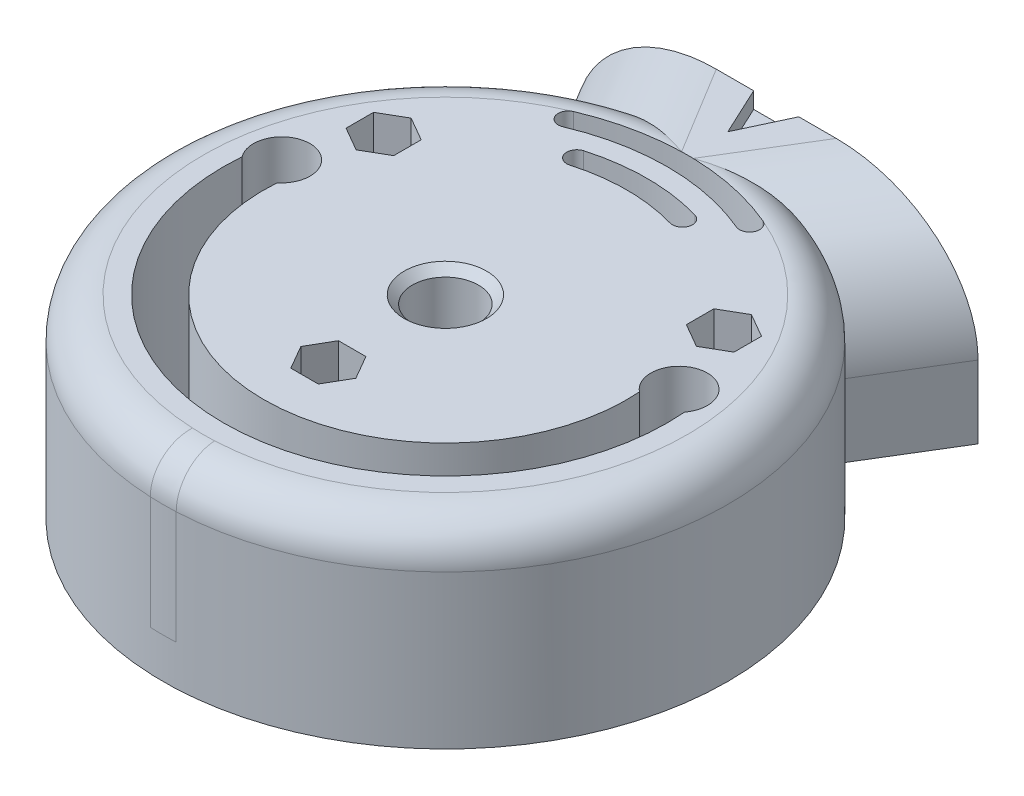
SolidWorks part; units mm, degrees
ref_plane "Alzado" through (0, 0, 0) normal (0, 0, 1) x (1, 0, 0)
ref_plane "Planta" through (0, 0, 0) normal (0, 1, 0) x (1, 0, 0)
ref_plane "Vista lateral" through (0, 0, 0) normal (1, 0, 0) x (0, 0, -1)
sketch "Croquis1" plane through (0, 0, 0) normal (0, 1, 0) x (1, 0, 0)
  line L0 (0, 35) -> (0, 41) construction
  line L1 (-35, 0) -> (-35, 35) construction
  line L2 (35, 0) -> (35, 35) construction
  line L3 (-35, 35) -> (35, 35) construction
  line L4 (0, 38) -> (-35, 38) construction
  line L5 (-35, 38) -> (35, 38) construction
  line L6 (35, 38) -> (35, 35) construction
  line L7 (-35, 38) -> (-35, 35) construction
  line L8 (0, 41) -> (-35, 41) construction
  line L9 (-35, 41) -> (-35, 38) construction
  line L10 (-25, 41) -> (25, 41)
  line L11 (-25, 41) -> (-18.2213, 29.8829)
  line L12 (25, 41) -> (18.2213, 29.8829)
  circle A0 centre (0, 0) radius 35
  circle A1 centre (0, 0) radius 4.1
  point P3 (0, 35)
  dimension "D1" = 70
  dimension "D4" = 8.2
  dimension "D2" = 6
  dimension "D3" = 50
  dimension "D5" = 11.1171
extrude "Saliente-Extruir1" add sketch "Croquis1" along normal blind 24 contours A0 | A0 L10 region at (0, 0, -37.0825) region at (0, 0, -34.0101)
sketch "Croquis2" plane through (0, 24, 0) normal (0, 1, 0) x (1, 0, 0)
  line L0 (0, 41) -> (0, -35) construction
  line L1 (-25, 41) -> (25, 41) construction
  line L2 (0, -33.75) -> (1.05, -33.75)
  line L3 (0, -33.75) -> (-1.05, -33.75)
  line L4 (-1.05, -33.75) -> (-1.55, -33.75) construction
  line L5 (1.05, -33.75) -> (1.55, -33.75) construction
  line L6 (-1.55, -33.75) -> (-1.6057, -34.9631) construction
  line L7 (1.55, -33.75) -> (1.6057, -34.9631) construction
  line L8 (-1.05, -33.75) -> (-1.6057, -34.9631)
  line L9 (1.05, -33.75) -> (1.6057, -34.9631)
  line L10 (-1.6057, -34.9631) -> (-3.3557, -34.8828) construction
  arc A0 (-18.2213, 29.8829) -> (18.2213, 29.8829) centre (0, 0) ccw construction
  circle A1 centre (0, 0) radius 33.75
  circle A2 centre (0, 0) radius 35
  arc M1 (-18.2213, 29.8829) -> (18.2213, 29.8829) centre (0, 0) ccw
  dimension "D1" = 1.25
  dimension "D2" = 2.1
  dimension "D3" = 0.5
  dimension "D4" = 0.5
  dimension "D5" = 1.75
extrude "Cortar-Extruir1" cut sketch "Croquis2" against normal blind 19 contours L9 L2 L3 L8 M1 region at (0, 24, 34.4127)
sketch "Croquis12" plane through (0, 0, -41) normal (0, 0, -1) x (-1, 0, 0)
  line L0 (0, 24) -> (0, 0) construction
  line L1 (25, 24) -> (-25, 24) construction
  line L3 (0, 12) -> (15, 12)
  line L7 (0, 12) -> (-15, 12)
  circle A0 centre (-15, 12) radius 1.65
  circle A1 centre (15, 12) radius 1.65
  dimension "D3" = 3.3
  dimension "D1" = 30
  dimension "D2" = 12
sketch "Croquis13" plane through (0, 0, 0) normal (0, -1, 0) x (1, 0, 0)
  line L0 (25, -41) -> (15, -41) construction
  line L1 (-25, -41) -> (25, -41) construction
  line L2 (15, -41) -> (15, -35) construction
  line L3 (15, -35) -> (12, -35) construction
  line L4 (15, -35) -> (18, -35) construction
  line L5 (18, -35) -> (12, -35)
  line L6 (18, -35) -> (18, -32.3)
  line L7 (18, -32.3) -> (12, -32.3)
  line L8 (12, -32.3) -> (12, -35)
  line L9 (0, -41) -> (0, 0) construction
  line L10 (-15, -35) -> (-18, -35) construction
  line L11 (-15, -35) -> (-12, -35) construction
  line L12 (-12, -32.3) -> (-12, -35)
  line L13 (-18, -32.3) -> (-12, -32.3)
  line L14 (-18, -35) -> (-18, -32.3)
  line L15 (-18, -35) -> (-12, -35)
  dimension "D1" = 10
  dimension "D2" = 6
  dimension "D3" = 6
  dimension "D4" = 2.7
sketch "Croquis8" plane through (0, 24, 0) normal (0, 1, 0) x (1, 0, 0)
  line L0 (0, 0) -> (0, 41) construction
  line L1 (0, 0) -> (-18.4123, 30.6439)
  line L2 (0, 0) -> (18.4123, 30.6439)
  line L9 (-1.6057, -34.9631) -> (-1.05, -33.75)
  line L10 (-1.6057, -34.9631) -> (-1.05, -33.75)
  line L11 (-1.05, -33.75) -> (1.05, -33.75)
  line L12 (-1.05, -33.75) -> (1.05, -33.75)
  line L13 (1.05, -33.75) -> (1.6057, -34.9631)
  line L14 (1.05, -33.75) -> (1.6057, -34.9631)
  line L15 (18.2213, 29.8829) -> (25, 41)
  line L16 (18.2213, 29.8829) -> (25, 41)
  line L17 (25, 41) -> (-25, 41)
  line L18 (25, 41) -> (-25, 41)
  line L19 (-25, 41) -> (-18.2213, 29.8829)
  line L20 (-25, 41) -> (-18.2213, 29.8829)
  circle A0 centre (0, 0) radius 35.75
  circle A1 centre (0, 0) radius 33.25
  arc A3 (-18.2213, 29.8829) -> (-1.6057, -34.9631) centre (0, 0) ccw
  arc A4 (-18.2213, 29.8829) -> (-1.6057, -34.9631) centre (0, 0) ccw
  arc A6 (1.6057, -34.9631) -> (18.2213, 29.8829) centre (0, 0) ccw
  arc A7 (1.6057, -34.9631) -> (18.2213, 29.8829) centre (0, 0) ccw
  dimension "D1" = 71.5
  dimension "D2" = 66.5
  dimension "D4" = 30.6439
  dimension "D3" = 0
extrude "Saliente-Extruir3" add sketch "Croquis8" against normal up to surface (24 mm away) contours A1 L0 A0 L1 | L0 A1 L2 A0 region at (-9.1115, 24, -32.8557) region at (9.1115, 24, -32.8557) up to face at (0, 0, 4.1)
fillet "Redondeo7" radius 15 2 edges at (21.6106, 24, -35.4414) (-21.6106, 24, -35.4414)
sketch "Croquis10" plane through (0, 24, 0) normal (0, 1, 0) x (1, 0, 0)
  line L0 (0, 41) -> (0, -35) construction
  line L1 (-7.4314, 41) -> (7.4314, 41) construction
  line L2 (0, 0) -> (-10.7451, 25.3139) construction
  line L3 (-10.7451, 25.3139) -> (-11.7219, 27.6151) construction
  line L4 (10.7451, 25.3139) -> (11.7219, 27.6151) construction
  line L5 (-8.7915, 20.7114) -> (-9.7683, 23.0126) construction
  line L6 (-8.7915, 20.7114) -> (-9.7683, 23.0126) construction
  line L7 (-8.7915, 20.7114) -> (-9.7683, 23.0126)
  line L8 (0, 0) -> (6.1996, 21.629) construction
  line L9 (6.1996, 21.629) -> (6.8885, 24.0323) construction
  line L10 (-6.1996, 21.629) -> (-6.8885, 24.0323) construction
  circle A0 centre (0, 0) radius 30
  circle A1 centre (0, 0) radius 27.5
  arc A2 (-1.6057, -34.9631) -> (1.6057, -34.9631) centre (0, 0) ccw construction
  arc A3 (-11.7219, 27.6151) -> (-10.7451, 25.3139) centre (-11.2335, 26.4645) ccw
  arc A4 (11.7219, 27.6151) -> (10.7451, 25.3139) centre (11.2335, 26.4645) cw
  circle A5 centre (0, 0) radius 25
  circle A6 centre (0, 0) radius 22.5
  arc A7 (6.1996, 21.629) -> (6.8885, 24.0323) centre (6.544, 22.8306) ccw
  arc A8 (-6.1996, 21.629) -> (-6.8885, 24.0323) centre (-6.544, 22.8306) cw
  point P19 (-8.7915, 20.7114)
  dimension "D1" = 60
  dimension "D2" = 55
  dimension "D4" = 50
  dimension "D5" = 45
  dimension "D3" = 23
extrude "Cortar-Extruir5" cut sketch "Croquis10" against normal blind 29 contours A4 A0 A3 A1 | A8 A6 A7 A5 region at (0, 24, -23.3638) region at (0, 24, -27.8649)
sketch "Croquis11" plane through (0, 24, 0) normal (0, 1, 0) x (1, 0, 0)
  line L0 (-21.1734, 3.7334) -> (-22.1582, 3.9071) construction
  line L2 (0, 0) -> (0, -35) construction
  arc A0 (-27.4097, 2.2272) -> (27.4097, 2.2272) centre (0, 0) ccw
  arc A1 (-22.443, 1.6008) -> (22.443, 1.6008) centre (0, 0) ccw
  arc A2 (-1.6057, -34.9631) -> (1.6057, -34.9631) centre (0, 0) ccw construction
  arc A3 (-22.443, 1.6008) -> (-27.4097, 2.2272) centre (-24.6202, 4.3412) ccw
  arc A4 (22.443, 1.6008) -> (27.4097, 2.2272) centre (24.6202, 4.3412) cw
  dimension "D1" = 55
  dimension "D2" = 45
  dimension "D4" = 7
  dimension "D3" = 100
extrude "Cortar-Extruir6" cut sketch "Croquis11" against normal blind 29
extrude "Cortar-Extruir11" cut sketch "Croquis13" against normal blind 12
sketch "Croquis15" plane through (0, 0, -32.3) normal (0, 0, -1) x (-1, 0, 0)
  line L0 (-18, 12) -> (-12, 12) construction
  line L1 (-15, 8.5359) -> (-12, 10.2679)
  line L2 (-12, 10.2679) -> (-12, 13.7321)
  line L3 (-12, 13.7321) -> (-15, 15.4641)
  line L4 (-15, 15.4641) -> (-18, 13.7321)
  line L5 (-18, 13.7321) -> (-18, 10.2679)
  line L6 (-18, 10.2679) -> (-15, 8.5359)
  line L7 (0, 24) -> (0, 0) construction
  line L8 (-11.7219, 0) -> (11.7219, 0) construction
  line L9 (18, 10.2679) -> (15, 8.5359)
  line L10 (18, 13.7321) -> (18, 10.2679)
  line L11 (15, 15.4641) -> (18, 13.7321)
  line L12 (12, 13.7321) -> (15, 15.4641)
  line L13 (12, 10.2679) -> (12, 13.7321)
  line L14 (15, 8.5359) -> (12, 10.2679)
  circle A0 centre (-15, 12) radius 3 construction
  circle A1 centre (15, 12) radius 3 construction
  dimension "D1" = 6
extrude "Cortar-Extruir13" cut sketch "Croquis15" along normal blind 2.7
extrude "Cortar-Extruir14" cut sketch "Croquis12" against normal blind 15 contours A0 | A1 region at (-15, 13.6033, -41) region at (16.6033, 12, -41)
chamfer "Chaflán1" distance 1 angle 45 1 edges at (0, 24, 4.1)
chamfer "Chaflán2" distance 1 angle 45 1 edges at (0, 0, 4.1)
sketch "Croquis16" plane through (0, 5, 0) normal (0, 1, 0) x (1, 0, 0)
  line L0 (-1.05, -33.75) -> (1.05, -33.75)
  line L1 (1.05, -33.75) -> (1.6057, -34.9631)
  line L2 (-1.05, -33.75) -> (-1.6057, -34.9631)
  arc A0 (-1.6057, -34.9631) -> (1.6057, -34.9631) centre (0, 0) ccw construction
  spline S0 degree 2 poles (-1.6057, -34.9631) (0, -35.0369) (1.6057, -34.9631) knots 0 0 0 1 1 1
extrude "Saliente-Extruir4" add sketch "Croquis16" along normal up to surface (19 mm away) up to face at (0, 24, 5.1)
fillet "Redondeo18" radius 5 3 edges at (34.9849, 24, 1.0281) (-34.9849, 24, 1.0281)
sketch "Croquis17" plane through (0, 24, 0) normal (0, 1, 0) x (1, 0, 0)
  line L0 (0, 25) -> (0, 0) construction
  line L1 (0, 0) -> (21.0848, 13.4325) construction
  line L2 (0, 0) -> (0, -25) construction
  circle A0 centre (0, 0) radius 25 construction
  circle A1 centre (21.0848, 13.4325) radius 1.6
  circle A3 centre (0, -14.5) radius 1.6
  circle A4 centre (-21.0848, 13.4325) radius 1.6
  dimension "D1" = 50
  dimension "D3" = 3.2
  dimension "D2" = 122.5
  dimension "D4" = 14.5
extrude "Cortar-Extruir15" cut sketch "Croquis17" against normal blind 40 contours A3 | A4 A0 | A4 A0 | A0 A1 | A0 A1 region at (21.0848, 24, -13.4325) region at (0, 24, 14.5) region at (-21.0848, 24, -13.4325)
sketch "Croquis18" plane through (0, 24, 0) normal (0, 1, 0) x (1, 0, 0)
  line L0 (-21.0848, 16.8394) -> (-21.0848, 10.0255) construction
  line L1 (-21.0848, 16.8394) -> (-24.0353, 15.136)
  line L2 (-24.0353, 15.136) -> (-24.0353, 11.729)
  line L3 (-24.0353, 11.729) -> (-21.0848, 10.0255)
  line L4 (-21.0848, 10.0255) -> (-18.1343, 11.729)
  line L5 (-18.1343, 11.729) -> (-18.1343, 15.136)
  line L6 (-18.1343, 15.136) -> (-21.0848, 16.8394)
  line L7 (0, -11.5495) -> (0, -17.4505) construction
  line L8 (3.4069, -14.5) -> (1.7035, -11.5495)
  line L9 (1.7035, -11.5495) -> (-1.7035, -11.5495)
  line L10 (-1.7035, -11.5495) -> (-3.4069, -14.5)
  line L11 (-3.4069, -14.5) -> (-1.7035, -17.4505)
  line L12 (-1.7035, -17.4505) -> (1.7035, -17.4505)
  line L13 (1.7035, -17.4505) -> (3.4069, -14.5)
  line L14 (21.0848, 16.8394) -> (21.0848, 10.0255) construction
  line L15 (21.0848, 16.8394) -> (18.1343, 15.136)
  line L16 (18.1343, 15.136) -> (18.1343, 11.729)
  line L17 (18.1343, 11.729) -> (21.0848, 10.0255)
  line L18 (21.0848, 10.0255) -> (24.0353, 11.729)
  line L19 (24.0353, 11.729) -> (24.0353, 15.136)
  line L20 (24.0353, 15.136) -> (21.0848, 16.8394)
  circle A0 centre (-21.0848, 13.4325) radius 2.9505 construction
  circle A1 centre (0, -14.5) radius 2.9505 construction
  circle A2 centre (21.0848, 13.4325) radius 2.9505 construction
  dimension "D1" = 5.901
extrude "Cortar-Extruir16" cut sketch "Croquis18" against normal blind 14
sketch "Croquis19" plane through (0, 24, 0) normal (0, 1, 0) x (1, 0, 0)
  line L0 (0, 41) -> (0, 30) construction
  line L1 (-7.4314, 41) -> (7.4314, 41) construction
  line L2 (0, 35) -> (-2.7978, 41)
  line L3 (0, 35) -> (2.7978, 41)
  line L4 (-2.7978, 41) -> (2.7978, 41)
  arc A0 (0.7188, 29.9914) -> (-0.7188, 29.9914) centre (0, 0) ccw construction
  dimension "D1" = 6
  dimension "D3" = 25
extrude "Cortar-Extruir17" cut sketch "Croquis19" against normal blind 2
